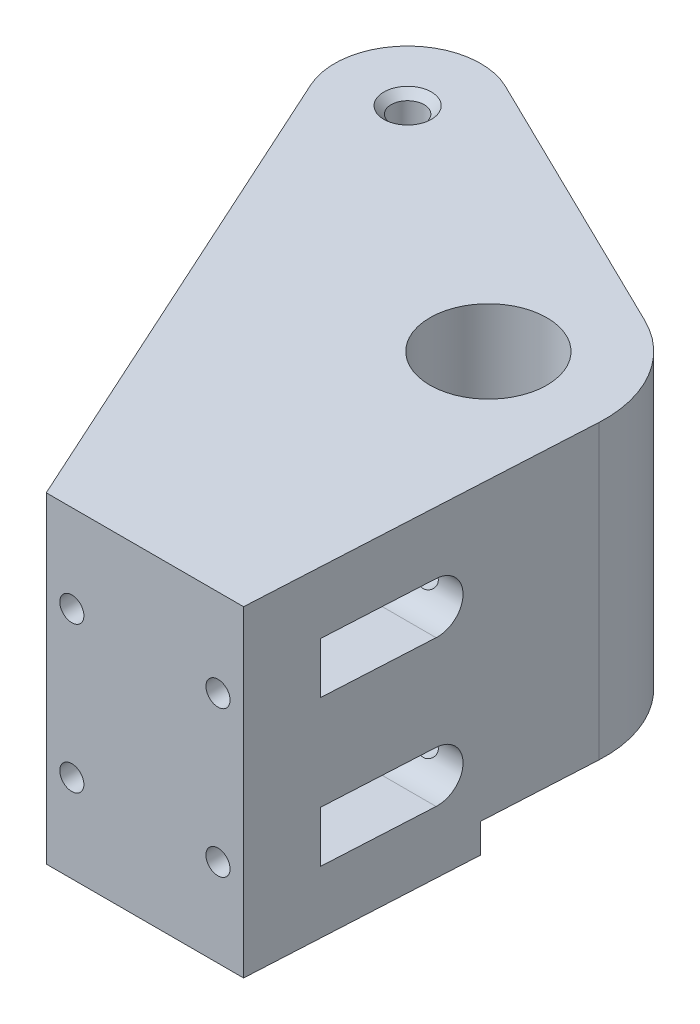
SolidWorks part; units mm, degrees
material "PET"
ref_plane "Front Plane" through (0, 0, 0) normal (0, 0, 1) x (1, 0, 0)
ref_plane "Top Plane" through (0, 0, 0) normal (0, 1, 0) x (1, 0, 0)
ref_plane "Right Plane" through (0, 0, 0) normal (1, 0, 0) x (0, 0, -1)
sketch "Sketch1" plane through (0, 0, 0) normal (0, 1, 0) x (1, 0, 0)
  line L0 (0, 0) -> (0, 47) construction
  line L1 (-13.5, 0) -> (13.5, 0)
  line L2 (13.5, 0) -> (15.977, 46.1423)
  line L6 (-30.2615, 79.5856) -> (7.0216, 61.377)
  line L7 (-43.7514, 66.457) -> (-13.5, 0)
  circle A0 centre (0, 47) radius 8
  arc A1 (15.977, 46.1423) -> (7.0216, 61.377) centre (0, 47) ccw
  circle A2 centre (-34.65, 70.6) radius 2.25
  arc A3 (-30.2615, 79.5856) -> (-43.7514, 66.457) centre (-34.65, 70.6) ccw
  dimension "D2" = 32
  dimension "D3" = 16
  dimension "D4" = 47
  dimension "D5" = 34.65
  dimension "D6" = 23.6
  dimension "D7" = 4.5
  dimension "D8" = 20
  dimension "D1" = 27
extrude "Boss-Extrude1" add sketch "Sketch1" along normal blind 44
sketch "Sketch2" plane through (0, 0, 0) normal (0, -1, 0) x (1, 0, 0)
  line L0 (0, -30.75) -> (15.1507, -30.75)
  line L1 (13.5, 0) -> (15.977, -46.1423) construction
  line L2 (15.1507, -30.75) -> (16.5451, -56.7258)
  line L8 (0, -30.75) -> (-44.65, -30.75)
  line L9 (-44.65, -30.75) -> (-44.65, -86.6128)
  line L10 (-44.65, -86.6128) -> (16.5451, -56.7258)
  line L11 (7.0216, -61.377) -> (-30.2615, -79.5856) construction
  arc A1 (-43.7514, -66.457) -> (-30.2615, -79.5856) centre (-34.65, -70.6) ccw construction
  circle A2 centre (0, -47) radius 8 construction
  dimension "D1" = 16.25
extrude "Cut-Extrude4" cut sketch "Sketch2" against normal blind 4
sketch "Sketch4" plane through (0, 0, 0) normal (0, 0, 1) x (1, 0, 0)
  line L0 (-16, 0) -> (-44.65, 37)
  line L1 (-27.4975, 0) -> (-13.5, 0) construction
  line L2 (-44.65, 44) -> (-44.65, 4) construction
  line L3 (-44.65, 37) -> (-44.65, 0)
  line L4 (-44.65, 0) -> (-16, 0)
  dimension "D1" = 16
  dimension "D2" = 7
extrude "Cut-Extrude5" cut sketch "Sketch4" against normal through all
sketch "Sketch5" plane through (0, 4, 0) normal (0, -1, 0) x (1, 0, 0)
  circle A0 centre (0, -47) radius 12 construction
  dimension "D1" = 24
hole_wizard "Ø4.5 (4.5) Diameter Hole1" positions "Sketch6" profile "Sketch8" hole size "Ø4.5" standard "ANSI Metric"
sketch "Sketch6" plane through (0, 4, 0) normal (0, -1, 0) x (-1, 0, 0)
  circle A0 centre (0, 47) radius 12 construction
  point P0 (0, 35)
  point P4 (0, 59)
  point P6 (12, 47)
  point P8 (-12, 47)
sketch "Sketch8" plane through (0, 4, -35) normal (1, 0, 0) x (0, 0, -1)
  line L0 (0, 0) -> (0, 11.3519)
  line L1 (0, 11.3519) -> (2.25, 10)
  line L2 (2.25, 10) -> (2.25, 0)
  line L5 (2.25, 0) -> (0, 0)
  line L10 (0, 11.3519) -> (-2.25, 10) construction
  line L11 (0, -6.35) -> (0, 107.95) construction
  dimension "Hole Dia." = 4.5
  dimension "Hole Depth" = 10
  dimension "Drill Angle" = 118
chamfer "Chamfer1" distance 1 angle 45 5 edges at (-34.65, 44, -68.35) (0, 4, -37.25) (-12, 4, -49.25) (0, 4, -61.25) (12, 4, -49.25)
sketch "Sketch9" plane through (0, 0, 0) normal (0, 0, 1) x (1, 0, 0)
  line L0 (0, 0) -> (0, 44) construction
  line L1 (-13.5, 44) -> (13.5, 44) construction
  line L2 (13.5, 22) -> (-13.5, 22) construction
  line L3 (13.5, 44) -> (13.5, 0) construction
  line L4 (-13.5, 44) -> (-13.5, 0) construction
  line L6 (10, 32) -> (-10, 32) construction
  line L7 (10, 32) -> (10, 12) construction
  line L8 (10, 12) -> (-10, 12) construction
  line L9 (-10, 32) -> (-10, 12) construction
  line L10 (10, 32) -> (-10, 12) construction
  line L11 (10, 12) -> (-10, 32) construction
  point P11 (0, 22)
  dimension "D1" = 20
  dimension "D2" = 20
hole_wizard "Ø3.3 (3.3) Diameter Hole1" positions "Sketch10" profile "Sketch12" hole size "Ø3.3" standard "ANSI Metric" end condition through all
sketch "Sketch10" plane through (0, 0, 0) normal (0, 0, 1) x (1, 0, 0)
  point P0 (-10, 32)
  point P3 (10, 32)
  point P6 (10, 12)
  point P9 (-10, 12)
sketch "Sketch12" plane through (-10, 32, 0) normal (1, 0, 0) x (0, -1, 0)
  line L0 (0, 0) -> (0, 80.6)
  line L1 (0, 80.6) -> (1.65, 80.6)
  line L2 (1.65, 80.6) -> (1.65, 0)
  line L5 (1.65, 0) -> (0, 0)
  line L11 (0, -6.35) -> (0, 107.95) construction
  dimension "Thru Hole Dia." = 3.3
  dimension "Thru Hole Depth" = 80.6
sketch "Sketch13" plane through (0, 0, 0) normal (1, 0, 0) x (0, 0, -1)
  line L0 (0, 22) -> (46.1423, 22) construction
  line L1 (10, 35.5) -> (25, 35.5)
  line L2 (10, 35.5) -> (10, 28.5)
  line L3 (10, 28.5) -> (25, 28.5)
  line L5 (10, 35.5) -> (25, 28.5) construction
  line L6 (10, 28.5) -> (25, 35.5) construction
  line L7 (10, 15.5) -> (25, 15.5)
  line L8 (10, 15.5) -> (10, 8.5)
  line L9 (10, 8.5) -> (25, 8.5)
  line L11 (10, 15.5) -> (25, 8.5) construction
  line L12 (10, 8.5) -> (25, 15.5) construction
  line L13 (46.1423, 44) -> (46.1423, 4) construction
  line L14 (0, 0) -> (0, 44) construction
  arc A0 (25, 28.5) -> (25, 35.5) centre (25, 32) ccw
  arc A1 (25, 8.5) -> (25, 15.5) centre (25, 12) ccw
  point P0 (17.5, 32)
  point P5 (17.5, 12)
  dimension "D1" = 7
  dimension "D2" = 7
  dimension "D3" = 15
  dimension "D4" = 15
  dimension "D5" = 10
  dimension "D6" = 10
  dimension "D7" = 10
  dimension "D8" = 10
extrude "Cut-Extrude6" cut sketch "Sketch13" against normal through all both and the other way through all
